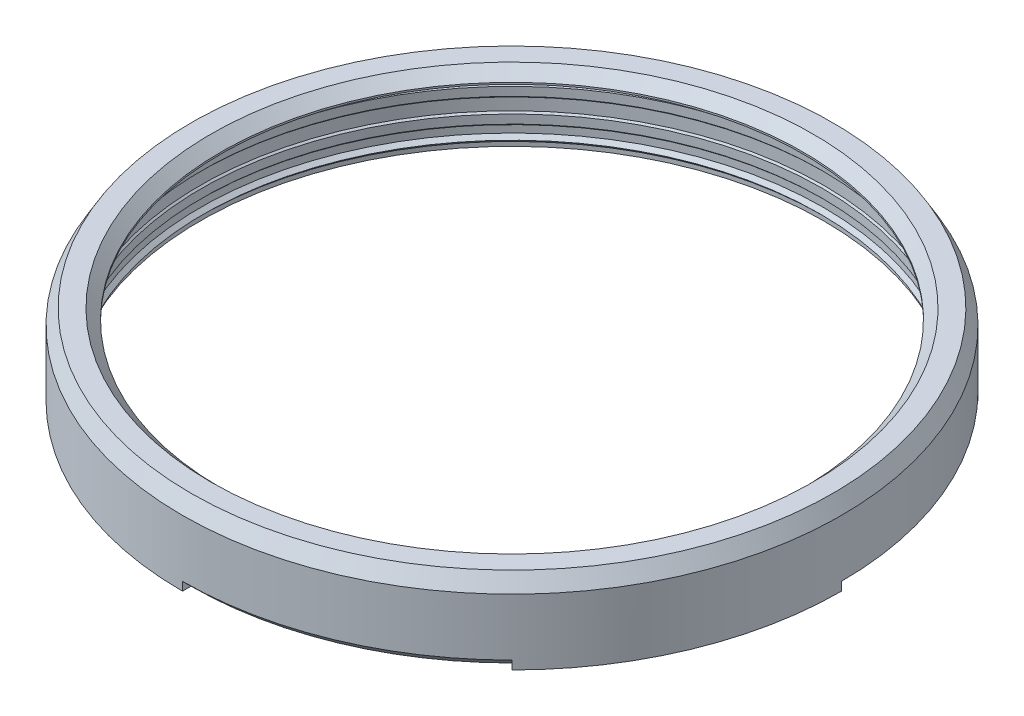
SolidWorks part; units mm, degrees
ref_plane "前视基准面" through (0, 0, 0) normal (0, 0, 1) x (1, 0, 0)
ref_plane "上视基准面" through (0, 0, 0) normal (0, 1, 0) x (1, 0, 0)
ref_plane "右视基准面" through (0, 0, 0) normal (1, 0, 0) x (0, 0, -1)
sketch "草图1" plane through (0, 0, 0) normal (0, 1, 0) x (1, 0, 0)
  circle A0 centre (0, 0) radius 38.5
  dimension "D1" = 77
extrude "凸台-拉伸1" add sketch "草图1" along normal blind 2
sketch "草图2" plane through (0, 0, 0) normal (0.3584, 0, 0.9336) x (0.9336, 0, -0.3584)
  line L0 (36.43, -8) -> (36.43, -7.5)
  line L1 (36.43, -7.5) -> (36.005, -7.075)
  line L2 (36.005, -7.075) -> (36.43, -6.65)
  line L3 (36.43, -6.65) -> (36.43, -5.8)
  line L4 (36.43, -5.8) -> (36.24, -5.61)
  line L5 (36.24, -5.61) -> (36.24, -4.59)
  line L6 (36.24, -4.59) -> (36.43, -4.4)
  line L7 (36.43, -4.4) -> (36.43, -3)
  line L8 (36.43, -3) -> (36.24, -2.81)
  line L9 (36.24, -2.81) -> (36.24, -1.79)
  line L10 (36.24, -1.79) -> (36.43, -1.6)
  line L11 (36.43, -1.6) -> (36.43, -1.4)
  line L12 (35.03, 0) -> (38.5, 0)
  line L13 (38.5, 0) -> (38.5, -8)
  line L14 (38.5, -8) -> (36.43, -8)
  line L15 (36.3, -8) -> (37.5, -8) construction
  line L16 (36.3, -8) -> (36.3, -7.5) construction
  line L17 (0, 0) -> (0, 8.3038) construction
  arc A0 (36.43, -1.4) -> (35.03, 0) centre (35.03, -1.4) ccw
  dimension "D9" = 1.4
  dimension "D1" = 2.26
  dimension "D2" = 8
  dimension "D3" = 0.5
  dimension "D4" = 0.85
  dimension "D5" = 1.4
  dimension "D6" = 1.02
  dimension "D7" = 1.02
  dimension "D8" = 0.2
  dimension "D10" = 135
  dimension "D11" = 0.13
revolve "旋转1" add sketch "草图2" angle 360 about L17
sketch "草图3" plane through (0, 2, 0) normal (0, 1, 0) x (1, 0, 0)
  circle A0 centre (0, 0) radius 34
  circle A1 centre (0, 0) radius 38.5 construction
  dimension "D1" = 4.5
extrude "切除-拉伸1" cut sketch "草图3" against normal through all
sketch "草图4" plane through (0, 2, 0) normal (0, 1, 0) x (1, 0, 0)
  circle A1 centre (0, 0) radius 38.5
  circle A2 centre (0, 0) radius 38.5
  dimension "D1" = 0
extrude "切除-拉伸2" cut sketch "草图4" against normal blind 0.6
chamfer "倒角1" distance 1.732 angle 30 1 edges at (0, 1.4, 38.5) first distance on face at (0, -8, -38.5)
chamfer "倒角2" distance 1.2 angle 45 1 edges at (0, 1.4, 34)
sketch "草图5" plane through (0, 0, 0) normal (0, 0, 1) x (1, 0, 0)
  line L0 (38.5, -8) -> (38.5, -7)
  line L1 (38.5, -7) -> (37.5, -8)
  line L2 (-38.5, -8) -> (38.5, -8) construction
  line L3 (37.5, -8) -> (38.5, -8)
  line L4 (0, 0) -> (0, 5.1701) construction
  dimension "D1" = 1
  dimension "D2" = 1
revolve "切除-旋转1" cut sketch "草图5" angle 45 about L4
pattern_circular "阵列(圆周)1" count 4 over 360 about axis through (0, 0, 0) along (0, 1, 0) of "切除-旋转1" reverse direction yes
sketch "草图6" plane through (0, 0, 0) normal (0, -1, 0) x (1, 0, 0)
  circle A0 centre (0, 0) radius 34.82
  circle A1 centre (0, 0) radius 35.28
  circle A2 centre (0, 0) radius 34 construction
  dimension "D1" = 0.82
  dimension "D2" = 0.46
extrude "凸台-拉伸2" add sketch "草图6" along normal blind 0.5
